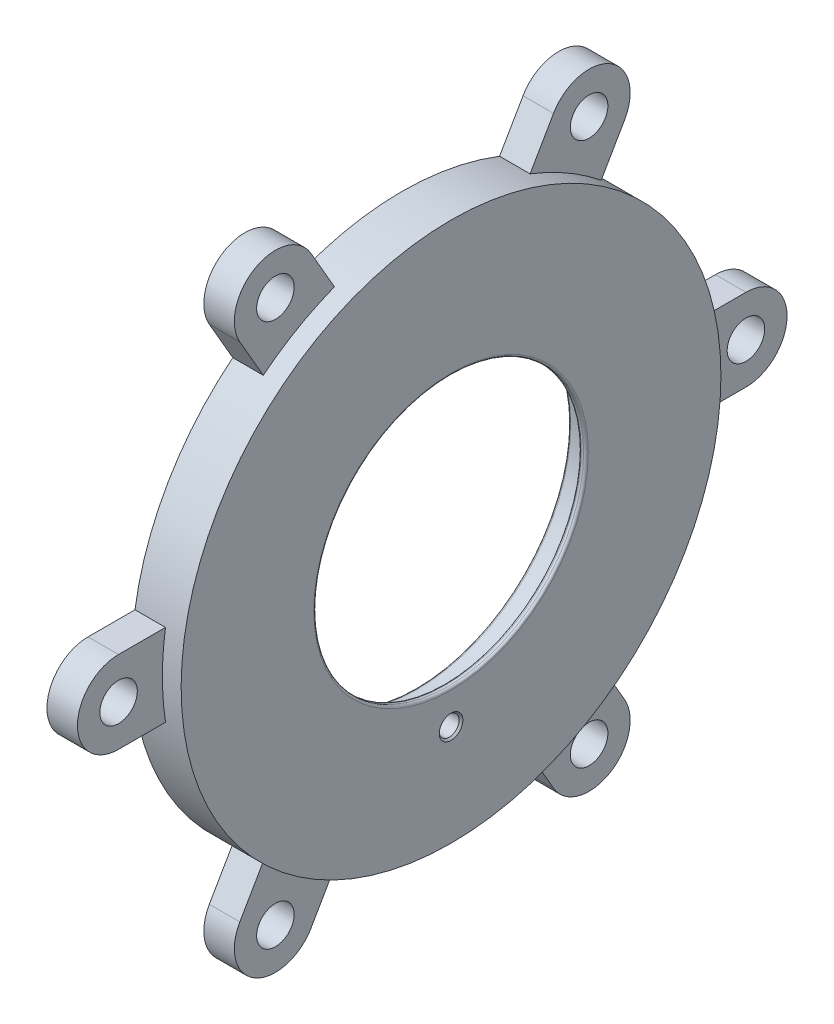
SolidWorks part; units mm, degrees
ref_plane "Front Plane" through (0, 0, 0) normal (0, 0, 1) x (1, 0, 0)
ref_plane "Top Plane" through (0, 0, 0) normal (0, 1, 0) x (1, 0, 0)
ref_plane "Right Plane" through (0, 0, 0) normal (1, 0, 0) x (0, 0, -1)
sketch "Sketch2" plane through (0, 0, 0) normal (1, 0, 0) x (0, 0, -1)
  line L0 (113.6607, 17.5) -> (133.6607, 17.5)
  line L2 (113.6607, -17.5) -> (133.6607, -17.5)
  line L3 (71.9858, -89.683) -> (81.9858, -107.0035)
  line L4 (41.6749, -107.183) -> (51.6749, -124.5035)
  line L5 (-41.6749, -107.183) -> (-51.6749, -124.5035)
  line L6 (-71.9858, -89.683) -> (-81.9858, -107.0035)
  line L7 (-113.6607, -17.5) -> (-133.6607, -17.5)
  line L8 (-113.6607, 17.5) -> (-133.6607, 17.5)
  line L9 (-71.9858, 89.683) -> (-81.9858, 107.0035)
  line L10 (-41.6749, 107.183) -> (-51.6749, 124.5035)
  line L11 (41.6749, 107.183) -> (51.6749, 124.5035)
  line L12 (71.9858, 89.683) -> (81.9858, 107.0035)
  circle A0 centre (0, 0) radius 95
  circle A1 centre (0, 0) radius 115
  arc A2 (133.6607, 17.5) -> (133.6607, -17.5) centre (133.6607, 0) cw
  circle A3 centre (133.6607, 0) radius 8
  arc A4 (81.9858, -107.0035) -> (51.6749, -124.5035) centre (66.8303, -115.7535) cw
  circle A5 centre (66.8303, -115.7535) radius 8
  arc A6 (-51.6749, -124.5035) -> (-81.9858, -107.0035) centre (-66.8303, -115.7535) cw
  circle A7 centre (-66.8303, -115.7535) radius 8
  arc A8 (-133.6607, -17.5) -> (-133.6607, 17.5) centre (-133.6607, 0) cw
  circle A9 centre (-133.6607, 0) radius 8
  arc A10 (-81.9858, 107.0035) -> (-51.6749, 124.5035) centre (-66.8303, 115.7535) cw
  circle A11 centre (-66.8303, 115.7535) radius 8
  arc A12 (51.6749, 124.5035) -> (81.9858, 107.0035) centre (66.8303, 115.7535) cw
  circle A13 centre (66.8303, 115.7535) radius 8
  circle A14 centre (0, 0) radius 75
  circle A15 centre (0, 0) radius 65
  point P45 (0, 0)
  dimension "D1" = 190
  dimension "D3" = 20
  dimension "D5" = 16
  dimension "D7" = 150
  dimension "D8" = 130
  dimension "D4" = 35
  dimension "D2" = 20
  dimension "D6" = 6
extrude "Boss-Extrude1" add sketch "Sketch2" along normal blind 10 contours A0 A14 | A1 A0 | A8 L7 A1 L8 A9 | A10 L9 A1 L10 A11 | A12 L11 A1 L12 A13 | A2 L0 A1 L2 A3 | A4 L3 A1 L4 A5 | A6 L5 A1 L6 A7 region at (0, 16.987, -123.6607) region at (0, 8.5274, -111.4215) region at (0, 100.121, -57.8049) region at (0, -98.6482, -76.4577) region at (0, 100.121, 57.8049) region at (0, -115.5384, 47.2029) region at (0, 0, 115.513) region at (0, 0, 92.313)
extrude "Boss-Extrude2" add sketch "Sketch2<5>" against normal blind 3 contours A1 A0 | A2 L0 A1 L2 A3 | A12 L11 A1 L12 A13 | A10 L9 A1 L10 A11 | A8 L7 A1 L8 A9 | A6 L5 A1 L6 A7 | A4 L3 A1 L4 A5 region at (0, 16.987, -123.6607) region at (0, 8.5274, -111.4215) region at (0, 100.121, -57.8049) region at (0, -98.6482, -76.4577) region at (0, 100.121, 57.8049) region at (0, -115.5384, 47.2029) region at (0, 0, 115.513)
sketch "Sketch2<5>" plane through (0, 0, 0) normal (1, 0, 0) x (0, 0, -1) same geometry as "Sketch2"
fillet "Fillet1" radius 2.5 1 edges at (0, 0, -95)
extrude "Boss-Extrude3" add sketch "Sketch2<6>" along normal blind 12 from offset 3 contours A14 A15 region at (0, 0, 72.8787)
sketch "Sketch2<6>" plane through (0, 0, 0) normal (1, 0, 0) x (0, 0, -1) same geometry as "Sketch2"
sketch "Sketch3" plane through (15, 0, 0) normal (1, 0, 0) x (0, 0, -1)
  circle A0 centre (0, 0) radius 57.5
  circle A1 centre (0, 0) radius 115
  circle A2 centre (0, 0) radius 65
  circle A3 centre (0, 0) radius 65 construction
  circle M3 centre (0, 0) radius 65
  circle M4 centre (0, 0) radius 75
  dimension "D1" = 115
extrude "Boss-Extrude5" add sketch "Sketch3" along normal blind 3 contours A0 M3 | M4 M3 | A1 M4 region at (15, 0, 111.7473) region at (15, 0, 63.1615) region at (15, 0, 72.8787)
extrude "Boss-Extrude6" add sketch "Sketch3<3>" against normal up to next contours A1 M4 region at (15, 0, 111.7473)
sketch "Sketch3<3>" plane through (15, 0, 0) normal (1, 0, 0) x (0, 0, -1) same geometry as "Sketch3"
fillet "Fillet3" radius 1 6 edges at (18, 0, -57.5) (15, 0, -57.5) (15, 0, -65) (3, 0, -65) (3, 0, -75) (0, 0, -75)
hole_wizard "M10 Tapped Hole1" positions "Sketch6" profile "Sketch7" tap size "M10" standard "ISO"
sketch "Sketch6" plane through (18, 0, 0) normal (1, 0, 0) x (0, 0, -1)
  line L0 (0, 11.55) -> (0, -11.55) construction
  circle A0 centre (0, 0) radius 57.5 construction
  point P0 (0, -72)
  point P7 (0, -71.8645)
  dimension "D1" = 72
sketch "Sketch7" plane through (18, -72, 0) normal (0, 1, 0) x (0, 0, -1)
  line L0 (0, 0) -> (0, 12.5537)
  line L1 (0, 12.5537) -> (4.25, 10)
  line L2 (4.25, 10) -> (4.25, 0.775)
  line L3 (4.25, 0.775) -> (5.025, 0)
  line L5 (5.025, 0) -> (0, 0)
  line L6 (-4.25, 0.775) -> (-5.025, 0) construction
  line L10 (0, 12.5537) -> (-4.25, 10) construction
  line L11 (0, -6.35) -> (0, 107.95) construction
  dimension "Tap Drill Dia." = 8.5
  dimension "Tap Drill Depth" = 10
  dimension "Near C'Sink Dia." = 10.05
  dimension "Near C'Sink Angle" = 90
  dimension "Drill Angle" = 118
cosmetic thread "Hole Thread1" parameters "D1"=5, "D2"=10
hole_wizard "Ø6.0mm Dowel Hole1" positions "Sketch8" profile "Sketch10" hole size "Ø6.0" standard "ISO" end condition through all
sketch "Sketch8" plane through (0, 0, 0) normal (1, 0, 0) x (0, 0, -1)
  point P0 (0, -72)
sketch "Sketch10" plane through (0, -72, 0) normal (0, 1, 0) x (0, 0, 1)
  line L0 (0, 0) -> (0, 18)
  line L1 (0, 18) -> (3, 18)
  line L2 (3, 18) -> (3, 0)
  line L5 (3, 0) -> (0, 0)
  line L11 (0, -6.35) -> (0, 107.95) construction
  dimension "Thru Hole Dia." = 6
  dimension "Thru Hole Depth" = 18
